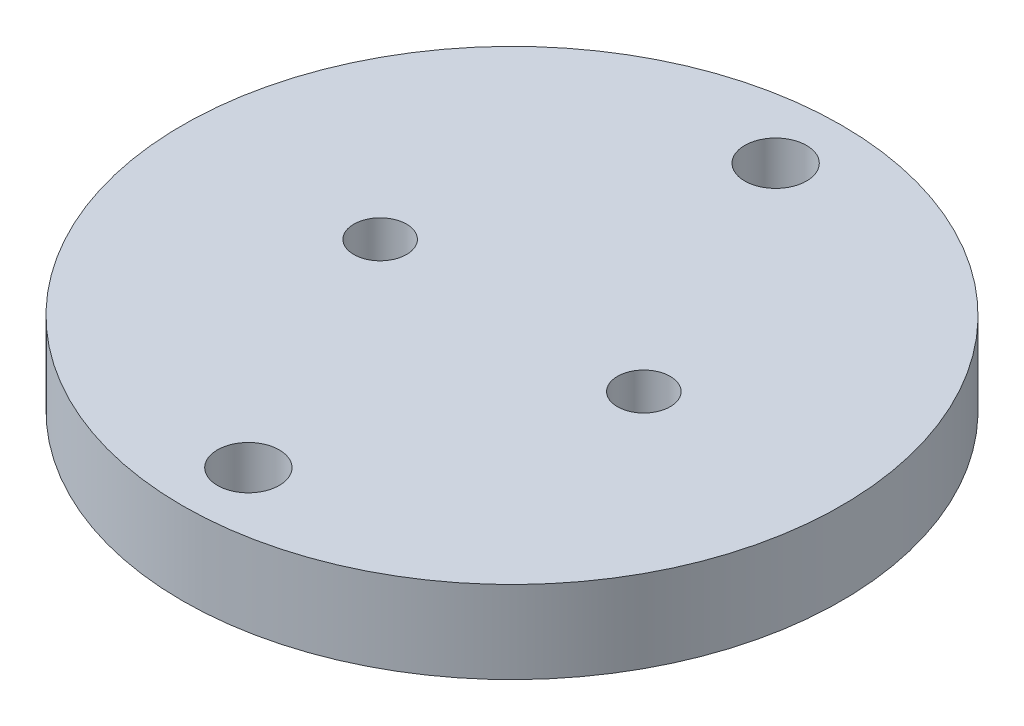
SolidWorks part; units mm, degrees
ref_plane "Front Plane" through (0, 0, 0) normal (0, 0, 1) x (1, 0, 0)
ref_plane "Top Plane" through (0, 0, 0) normal (0, 1, 0) x (1, 0, 0)
ref_plane "Right Plane" through (0, 0, 0) normal (1, 0, 0) x (0, 0, -1)
sketch "Sketch2" plane through (0, 0, 0) normal (0, 1, 0) x (1, 0, 0)
  circle A0 centre (0, 0) radius 12.7
  circle A1 centre (0, 10.16) radius 1.1906
  circle A4 centre (0, -10.16) radius 1.1906
  circle A5 centre (5.08, 0) radius 1.016
  circle A6 centre (-5.08, 0) radius 1.016
  dimension "D1" = 25.4
  dimension "D2" = 2.032
  dimension "D4" = 2.3813
  dimension "D5" = 2.3813
  dimension "D7" = 2.032
extrude "Boss-Extrude1" add sketch "Sketch2" along normal blind 3.175
